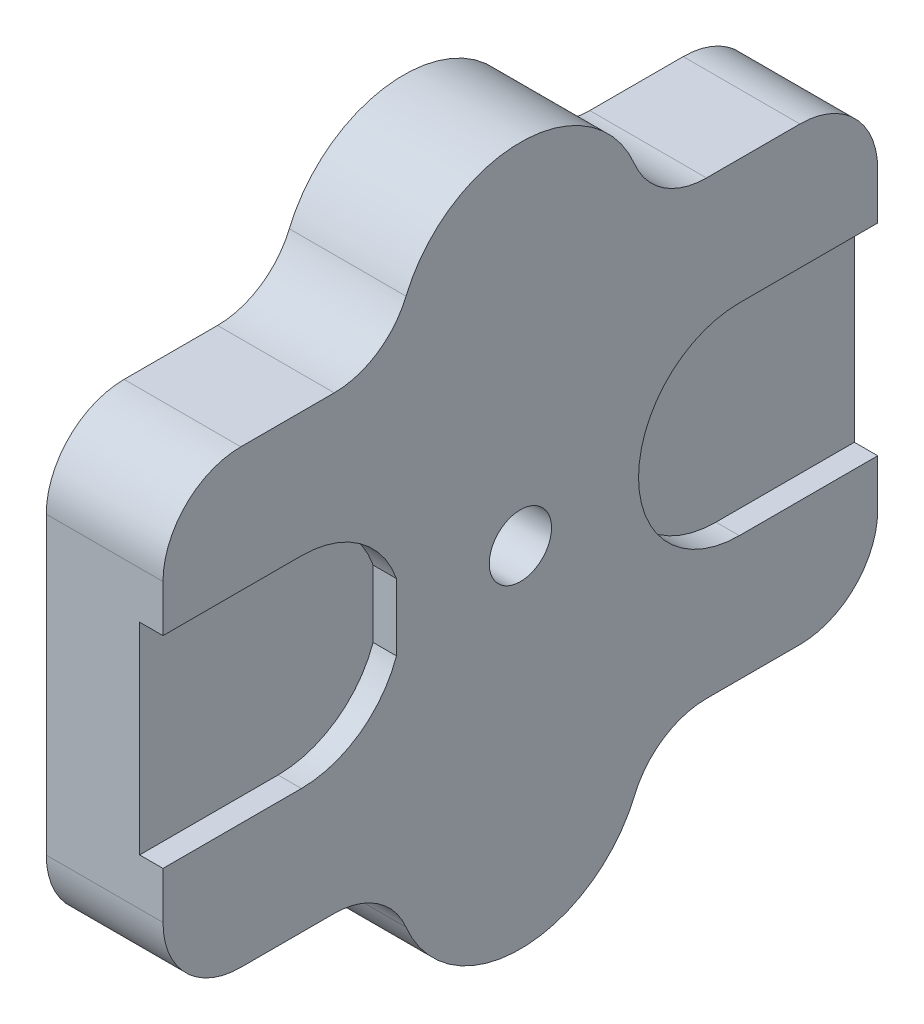
SolidWorks part; units mm, degrees
ref_plane "Front Plane" through (0, 0, 0) normal (1, 0, 0) x (0, 1, 0)
ref_plane "Top Plane" through (0, 0, 0) normal (0, 0, 1) x (0, 1, 0)
ref_plane "Right Plane" through (0, 0, 0) normal (0, 1, 0) x (-1, 0, 0)
sketch "Sketch1" plane through (0, 0, 0) normal (1, 0, 0) x (0, 1, 0)
  line L0 (-28.9545, 0) -> (33.8464, 0) construction
  line L3 (-28.9686, 19.054) -> (-28.9686, -12.7893) construction
  line L4 (0, 49.054) -> (0, -56.7378) construction
  line L6 (-28.9686, -12.7893) -> (28.9686, -12.7893)
  line L7 (44.5791, 0) -> (-44.5791, 0) construction
  line L9 (18.9686, 49.054) -> (-18.9686, 49.054)
  line L12 (-28.9686, 39.054) -> (-28.9686, 27.0474)
  line L13 (28.9686, 19.054) -> (28.9686, -12.7893) construction
  line L14 (28.9686, 39.054) -> (28.9686, 27.0474)
  line L15 (-28.9686, 19.054) -> (28.9686, 19.054) construction
  line L16 (-28.9686, 19.054) -> (28.9686, 19.054) construction
  arc A3 (-35.1108, 17.8215) -> (-28.9686, -12.7893) centre (-28.9686, 3.1323) ccw
  arc A4 (-18.9686, 49.054) -> (-28.9686, 39.054) centre (-18.9686, 39.054) ccw
  arc A5 (-35.1108, 17.8215) -> (-28.9686, 27.0474) centre (-38.9686, 27.0474) ccw
  arc A6 (35.1108, 17.8215) -> (28.9686, 27.0474) centre (38.9686, 27.0474) cw
  arc A7 (18.9686, 49.054) -> (28.9686, 39.054) centre (18.9686, 39.054) cw
  arc A8 (35.1108, 17.8215) -> (28.9686, -12.7893) centre (28.9686, 3.1323) cw
  point P20 (0, 0)
  dimension "D1" = 10
  dimension "D2" = 10
extrude "Boss-Extrude3" add sketch "Sketch1" along normal blind 15
sketch "Sketch3" plane through (15, 0, 0) normal (1, 0, 0) x (0, 1, 0)
  line L0 (-44.8903, 3.1323) -> (44.8903, 3.1323) construction
  line L2 (-28.9686, -12.7893) -> (28.9686, -12.7893) construction
  line L3 (0, -12.7893) -> (0, 49.054) construction
  line L4 (18.9686, 49.054) -> (-18.9686, 49.054) construction
  arc A3 (-35.1108, 17.8215) -> (-28.9686, -12.7893) centre (-28.9686, 3.1323) ccw construction
  arc A4 (28.9686, -12.7893) -> (35.1108, 17.8215) centre (28.9686, 3.1323) ccw construction
  circle A5 centre (0, 3.1323) radius 4
extrude "Cut-Extrude3" cut sketch "Sketch3" against normal blind 14.0462
sketch "Sketch4" plane through (15, 0, 0) normal (1, 0, 0) x (0, 1, 0)
  line L0 (-12.95, 49.054) -> (-12.95, 31.2677)
  line L4 (18.9686, 49.054) -> (-18.9686, 49.054) construction
  line L6 (0, 7.1323) -> (0, 31.2677) construction
  line L7 (12.95, 31.2677) -> (12.95, 49.054)
  line L8 (-12.95, 49.054) -> (12.95, 49.054)
  circle A1 centre (0, 3.1323) radius 4 construction
  circle A2 centre (0, 31.2677) radius 12.95 construction
  arc A3 (-12.95, 31.2677) -> (12.95, 31.2677) centre (0, 31.2677) ccw
extrude "Cut-Extrude4" cut sketch "Sketch4" against normal blind 3
sketch "Sketch5" plane through (15, 0, 0) normal (1, 0, 0) x (0, 1, 0)
  line L0 (-4, 3.1323) -> (49996, 3.1323) construction
ref_plane "Plane1" through (0, 0, 3.1323) normal (0, 0, 1) x (0, 1, 0)
mirror "Mirror1" about plane through (0, 0, 3.1323) normal (0, 0, 1) of "Boss-Extrude3", "Cut-Extrude3", "Cut-Extrude4"
